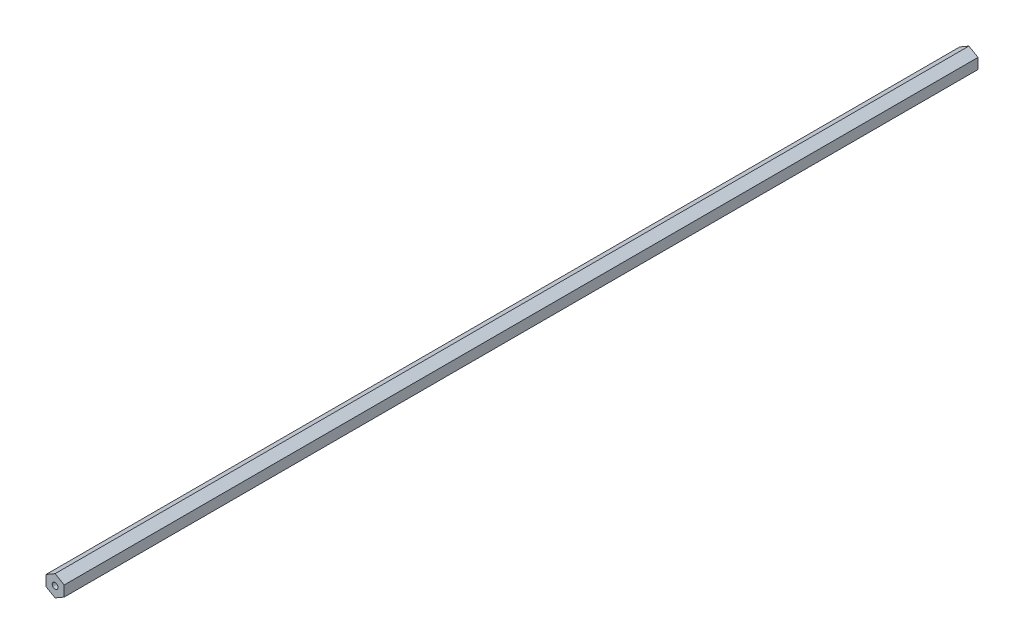
SolidWorks part; units mm, degrees
ref_plane "Front Plane" through (0, 0, 0) normal (0, 0, 1) x (1, 0, 0)
ref_plane "Top Plane" through (0, 0, 0) normal (0, 1, 0) x (1, 0, 0)
ref_plane "Right Plane" through (0, 0, 0) normal (1, 0, 0) x (0, 0, -1)
sketch "Sketch1" plane through (0, 0, 0) normal (0, 0, 1) x (1, 0, 0)
  line L1 (6.35, -3.6662) -> (6.35, 3.6662)
  line L2 (6.35, 3.6662) -> (0, 7.3323)
  line L3 (0, 7.3323) -> (-6.35, 3.6662)
  line L4 (-6.35, 3.6662) -> (-6.35, -3.6662)
  line L5 (-6.35, -3.6662) -> (0, -7.3323)
  line L6 (0, -7.3323) -> (6.35, -3.6662)
  circle A0 centre (0, 0) radius 6.35 construction
  dimension "D1" = 12.7
extrude "Boss-Extrude1" add sketch "Sketch1" along normal mid plane 637.667
sketch "Sketch2" plane through (0, 0, 318.8335) normal (0, 0, 1) x (1, 0, 0)
  circle A0 centre (0, 0) radius 2.4892
  dimension "D1" = 4.9784
hole_wizard "#10-32 Tapped Hole1" positions "3DSketch1" profile "Sketch3" tap size "#10-32" standard "ANSI Inch"
sketch3d "3DSketch1"
  line L1 (-6.35, 3.6662, -318.8335) -> (-6.35, -3.6662, -318.8335) construction
  point P0 (0, 0, 318.8335)
  point P3 (0, 0, -318.8335)
  point P13 (-6.35, 0, -318.8335)
sketch "Sketch3" plane through (0, 0, 318.8335) normal (1, 0, 0) x (0, -1, 0)
  line L0 (0, 0) -> (0, 17.5608)
  line L1 (0, 17.5608) -> (2.0193, 16.3474)
  line L2 (2.0193, 16.3474) -> (2.0193, 0)
  line L5 (2.0193, 0) -> (0, 0)
  line L10 (0, 17.5608) -> (-2.0193, 16.3474) construction
  line L11 (0, -6.35) -> (0, 107.95) construction
  dimension "Tap Drill Dia." = 4.0386
  dimension "Tap Drill Depth" = 16.3474
  dimension "Drill Angle" = 118
cosmetic thread "Hole Thread1" parameters "D1"=13.97, "D2"=4.826
cosmetic thread "Hole Thread2" parameters "D1"=13.97, "D2"=4.826
